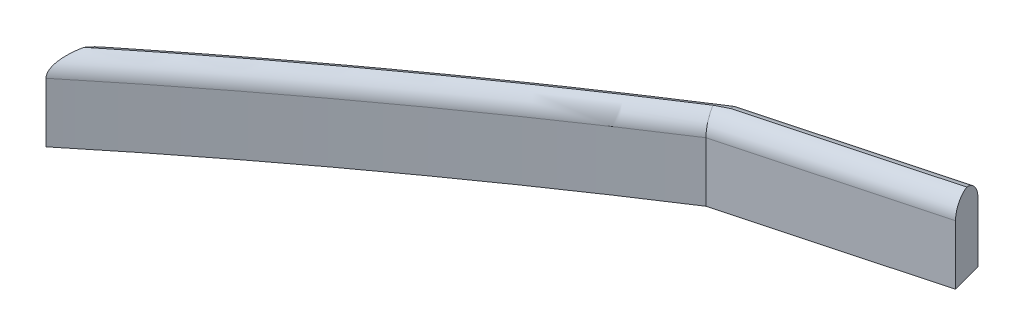
SolidWorks part; units mm, degrees
other "标注1"
sketch "草图3" plane through (-22.25, 4, -10) normal (-0.231, 0.6469, -0.7268) x (-0.9696, -0.2151, 0.1167)
other "标注2"
sketch "草图4" plane through (22.25, 8, -30) normal (0.0083, 0.0567, -0.9984) x (-0.9991, 0.0415, -0.0059)
ref_plane "前视基准面" through (0, 0, 0) normal (0, 0, 1) x (1, 0, 0)
ref_plane "上视基准面" through (0, 0, 0) normal (0, 1, 0) x (1, 0, 0)
ref_plane "右视基准面" through (0, 0, 0) normal (1, 0, 0) x (0, 0, -1)
other "Configuration Table"
sketch "草图1" plane through (0, 0, 0) normal (0, 1, 0) x (1, 0, 0)
  line L42 (-5.9281, -6.4493) -> (-4.8202, -3.7466)
  line L43 (23.2891, 10.2963) -> (13.3503, 7.6239)
  line L46 (-4.8202, -3.7466) -> (-3.3351, -4.3553)
  line L49 (13.3503, 9.291) -> (22.871, 11.851)
  line L50 (22.871, 11.851) -> (23.2891, 10.2963)
  arc A0 (13.3503, 7.6239) -> (-5.9281, -6.4493) centre (127.7719, -169.36) ccw
  arc A1 (13.3503, 9.291) -> (-4.8202, -3.7466) centre (127.7719, -169.36) ccw
  point P6 (23.0398, 10.2293)
  point P9 (22.9502, 10.2052)
  point P10 (0, 0)
  point P11 (0, 0)
  dimension "D3" = 210.75
  dimension "D4" = 1.605
  dimension "D5" = 2.921
  dimension "D6" = 6.105
  dimension "D7" = 4.8202
extrude "凸台-拉伸1" add sketch "草图1" along normal blind 4 contours A1 L46 A0 | A0 L46 L42 region at (-4.6948, 0, 4.8469) region at (4.2823, 0, -2.7482)
fillet "圆角1" radius 1 4 edges at (18.3197, 4, -8.9601) (18.1107, 4, -10.571) (3.5117, 4, -0.8604) (4.0932, 4, -3.0118)
